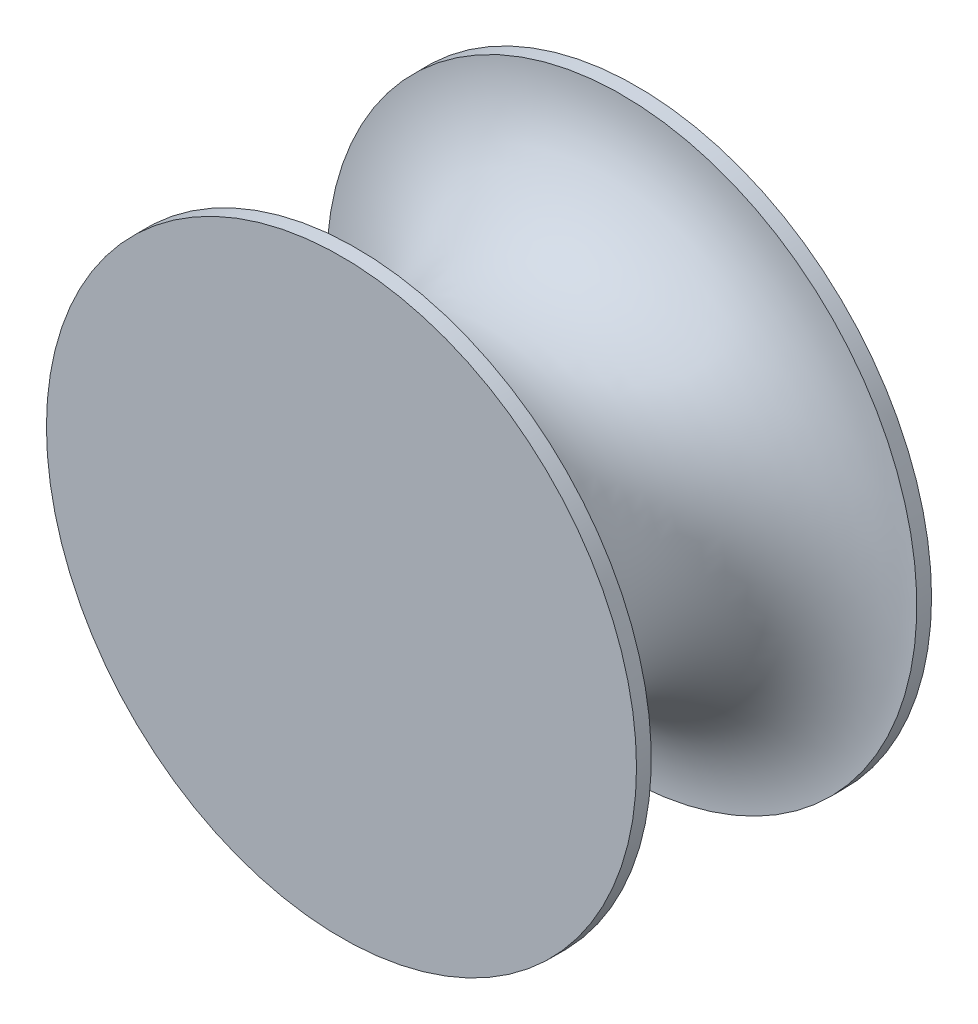
SolidWorks part; units mm, degrees
ref_plane "Front Plane" through (0, 0, 0) normal (0, 0, 1) x (1, 0, 0)
ref_plane "Top Plane" through (0, 0, 0) normal (0, 1, 0) x (1, 0, 0)
ref_plane "Right Plane" through (0, 0, 0) normal (1, 0, 0) x (0, 0, -1)
sketch "Sketch1" plane through (0, 0, 0) normal (0, 0, 1) x (1, 0, 0)
  circle A0 centre (0, 0) radius 12.7
extrude "Boss-Extrude1" add sketch "Sketch1" along normal blind 12.7
sketch "Sketch2" plane through (0, 0, 0) normal (1, 0, 0) x (0, 0, -1)
  line L0 (0, 12.7) -> (-12.7, 12.7) construction
  line L1 (-12.065, 12.7) -> (-0.635, 12.7)
  arc A0 (-12.065, 12.7) -> (-0.635, 12.7) centre (-6.35, 12.7) ccw
revolve "Cut-Revolve1" cut sketch "Sketch2" angle 360 about L0
sketch "Sketch4" plane through (0, 0, 0) normal (0, 0, -1) x (-1, 0, 0)
  circle A0 centre (0, 0) radius 7.62
extrude "Boss-Extrude2" add sketch "Sketch4" along normal blind 2.54
